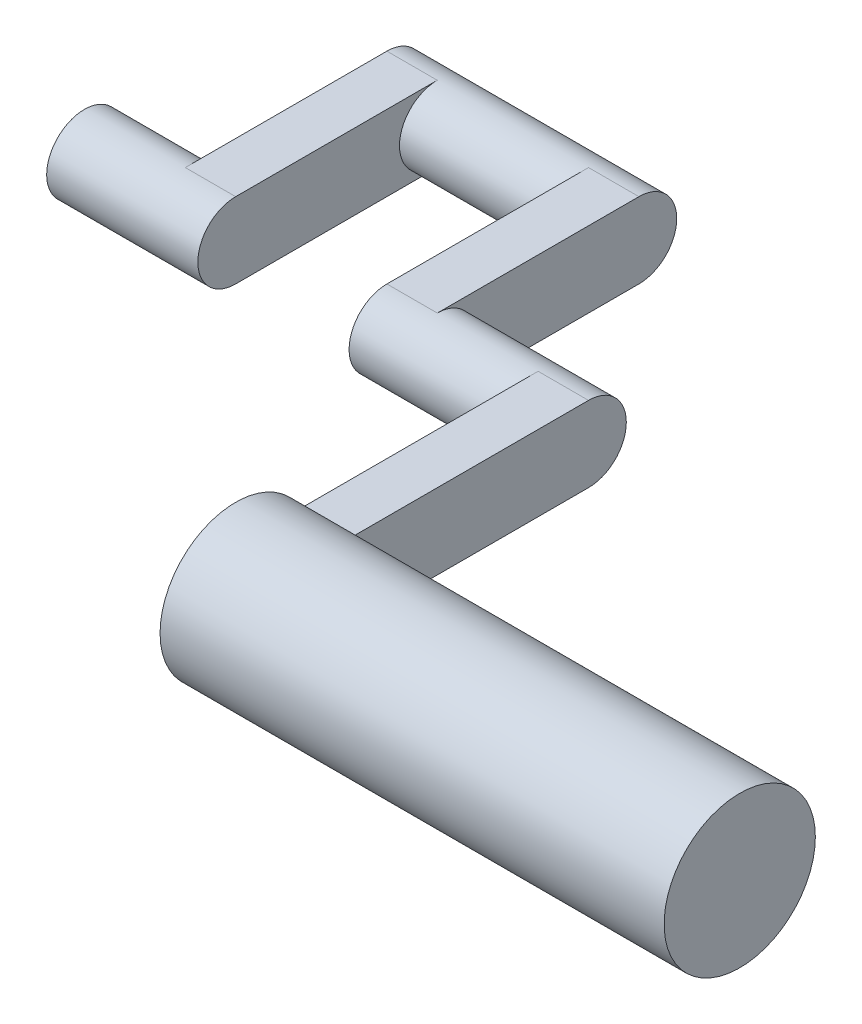
SolidWorks part; units mm, degrees
material "1060 Alloy"
ref_plane "Front Plane" through (0, 0, 0) normal (0, 0, 1) x (1, 0, 0)
ref_plane "Top Plane" through (0, 0, 0) normal (0, 1, 0) x (1, 0, 0)
ref_plane "Right Plane" through (0, 0, 0) normal (1, 0, 0) x (0, 0, -1)
sketch "Sketch1" plane through (0, 0, 0) normal (1, 0, 0) x (0, 0, -1)
  circle A0 centre (0, 0) radius 19.05
  dimension "D1" = 38.1
extrude "Boss-Extrude1" add sketch "Sketch1" against normal blind 127
sketch "Sketch2" plane through (-127, 0, 0) normal (-1, 0, 0) x (0, 0, 1)
  line L0 (-76.2, 9.525) -> (0, 9.525)
  line L1 (0, 9.525) -> (0, -9.525)
  line L2 (0, -9.525) -> (-76.2, -9.525)
  circle A0 centre (-76.2, 0) radius 9.525
  point P7 (0, 0)
  circle M2 centre (0, 0) radius 19.05
  dimension "D2" = 19.05
  dimension "D1" = 76.2
extrude "Boss-Extrude2" add sketch "Sketch2" against normal blind 12.7 contours A0 L2 L0 M2 | L2 L1 L0 M2 | A0 region at (-127, 0, -43.5104) region at (-127, 0, -76.2) region at (-127, 0, -9.1273)
extrude "Boss-Extrude3" add sketch "Sketch2<3>" along normal blind 38.1 contours A0 region at (-127, 0, -76.2)
sketch "Sketch2<3>" plane through (-127, 0, 0) normal (-1, 0, 0) x (0, 0, 1) same geometry as "Sketch2"
sketch "Sketch3" plane through (-165.1, 0, 0) normal (-1, 0, 0) x (0, 0, 1)
  line L0 (-127, 9.525) -> (-76.2, 9.525)
  line L1 (-127, -9.525) -> (-76.2, -9.525)
  circle A0 centre (-127, 0) radius 9.525
  circle A2 centre (-76.2, 0) radius 9.525
  circle A3 centre (-76.2, 0) radius 9.525
  circle M2 centre (-76.2, 0) radius 9.525
  dimension "D1" = 19.05
  dimension "D3" = 50.8
  dimension "D2" = 0
extrude "Boss-Extrude4" add sketch "Sketch3" against normal blind 12.7 contours A0 L1 L0 M2 | A0 region at (-165.1, 0, -101.6) region at (-165.1, 0, -127)
extrude "Boss-Extrude5" add sketch "Sketch3<3>" along normal blind 50.8 contours A0 region at (-165.1, 0, -127)
sketch "Sketch3<3>" plane through (-165.1, 0, 0) normal (-1, 0, 0) x (0, 0, 1) same geometry as "Sketch3"
extrude "Boss-Extrude6" add sketch "Sketch3<4>" against normal blind 12.7 from offset 50.8 contours A0 L1 L0 M2 | M2 region at (-165.1, 0, -101.6) region at (-165.1, 0, -76.2)
sketch "Sketch3<4>" plane through (-165.1, 0, 0) normal (-1, 0, 0) x (0, 0, 1) same geometry as "Sketch3"
extrude "Boss-Extrude7" add sketch "Sketch2<4>" along normal blind 25.4 from surface contours A0 region at (-127, 0, -76.2) starting at face at (-215.9, 0, -101.6)
sketch "Sketch2<4>" plane through (-127, 0, 0) normal (-1, 0, 0) x (0, 0, 1) same geometry as "Sketch2"
